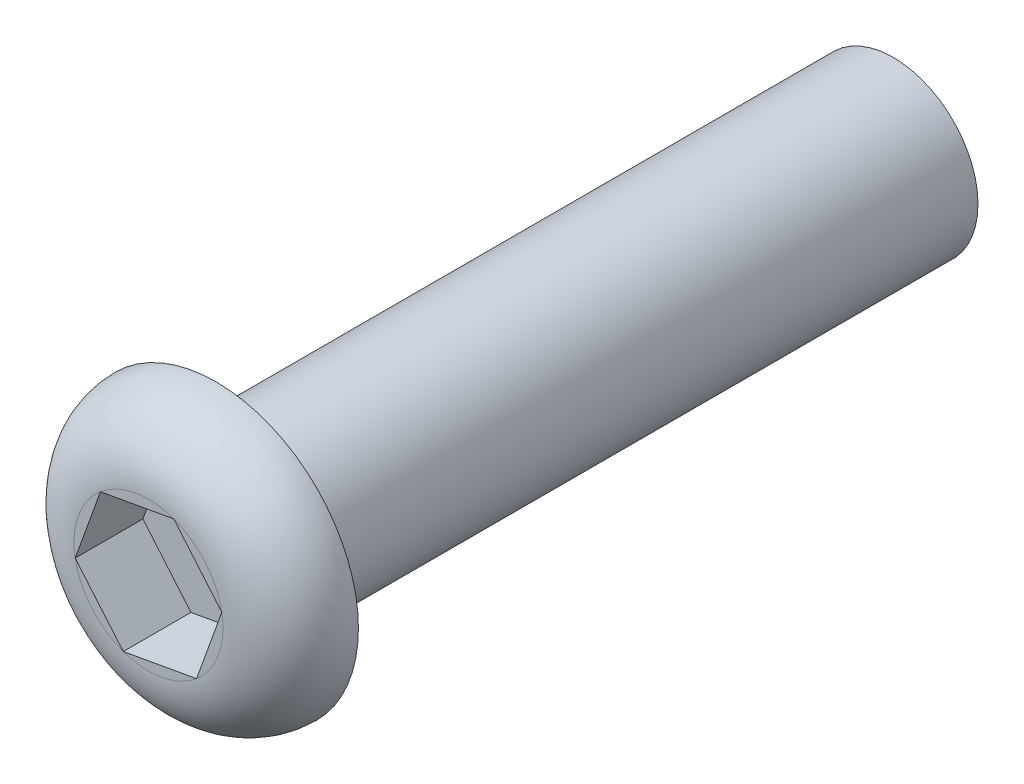
SolidWorks part; units mm, degrees
ref_plane "Front Plane" through (0, 0, 0) normal (0, 0, 1) x (1, 0, 0)
ref_plane "Top Plane" through (0, 0, 0) normal (0, 1, 0) x (1, 0, 0)
ref_plane "Right Plane" through (0, 0, 0) normal (1, 0, 0) x (0, 0, -1)
sketch "Sketch1" plane through (0, 0, 0) normal (0, 0, 1) x (1, 0, 0)
  circle A0 centre (0, 0) radius 3.175
  dimension "D1" = 6.35
extrude "Boss-Extrude1" add sketch "Sketch1" along normal blind 25.4
sketch "Sketch2" plane through (0, 0, 25.4) normal (0, 0, 1) x (1, 0, 0)
  circle A0 centre (0, 0) radius 5.334
  dimension "D1" = 10.668
extrude "Boss-Extrude2" add sketch "Sketch2" along normal blind 2.54
fillet "Fillet3" radius 2.54 1 edges at (5.334, 0, 27.94) type face fillet first side face at (5.334, 0, 27.94) second side face at (5.334, 0, 27.94)
sketch "Sketch6" plane through (0, 0, 27.94) normal (0, 0, 1) x (1, 0, 0)
  line L2 (1.8026, -2.1347) -> (2.75, 0.4937)
  line L3 (2.75, 0.4937) -> (0.9474, 2.6285)
  line L4 (0.9474, 2.6285) -> (-1.8026, 2.1347)
  line L5 (-1.8026, 2.1347) -> (-2.75, -0.4937)
  line L6 (-2.75, -0.4937) -> (-0.9474, -2.6285)
  line L7 (-0.9474, -2.6285) -> (1.8026, -2.1347)
  circle A0 centre (0, 0) radius 2.4197 construction
  circle A1 centre (0, 0) radius 2.794 construction
  dimension "D2" = 2.794
  dimension "D1" = 0.3743
  dimension "D3" = 2.794
  dimension "D4" = 2.1347
extrude "Cut-Extrude2" cut sketch "Sketch6" against normal blind 2.54 contours L2 L3 L4 L5 L6 L7
